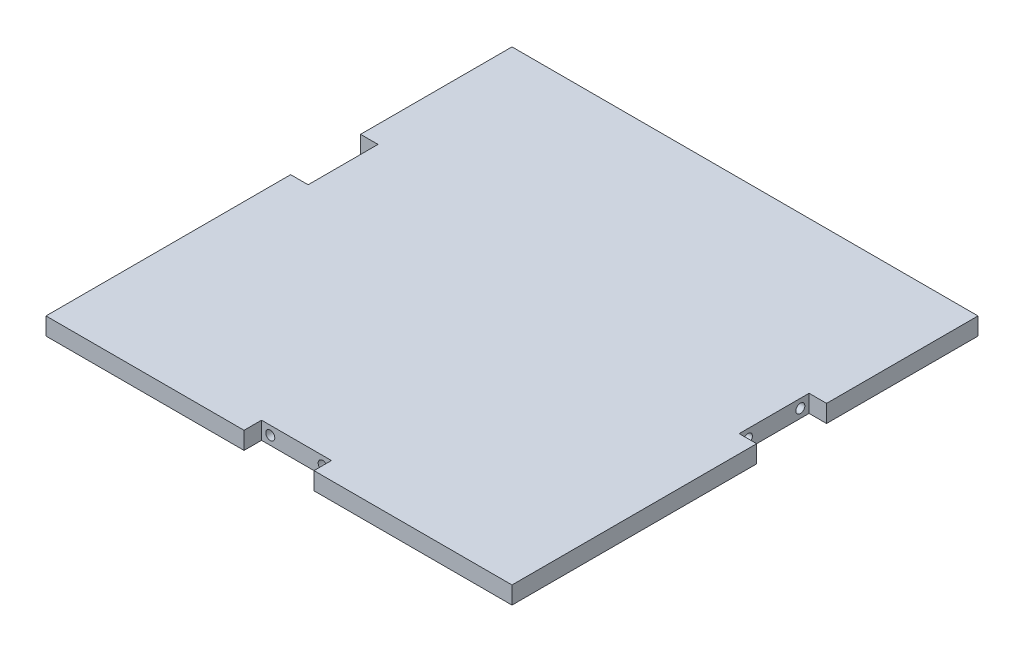
SolidWorks part; units mm, degrees
material "PE High Density"
ref_plane "Front Plane" through (0, 0, 0) normal (0, 0, 1) x (1, 0, 0)
ref_plane "Top Plane" through (0, 0, 0) normal (0, 1, 0) x (1, 0, 0)
ref_plane "Right Plane" through (0, 0, 0) normal (1, 0, 0) x (0, 0, -1)
sketch "Sketch1" plane through (0, 0, 0) normal (0, 1, 0) x (1, 0, 0)
  line L1 (-127, 127) -> (127, 127)
  line L2 (-127, 127) -> (-127, -127)
  line L3 (-127, -127) -> (127, -127)
  line L4 (127, 127) -> (127, -127)
  line L5 (-127, 127) -> (127, -127) construction
  line L6 (-127, -127) -> (127, 127) construction
  point P0 (0, 0)
  dimension "D1" = 254
  dimension "D2" = 254
extrude "Boss-Extrude1" add sketch "Sketch1" along normal blind 9.525
sketch "Sketch7" plane through (0, 9.525, 0) normal (0, 1, 0) x (1, 0, 0)
  line L0 (127, 127) -> (-127, 127) construction
  line L1 (-127, 25.4) -> (-41.0029, 25.4) construction
  line L2 (0, 0) -> (0, -32.6591) construction
  line L3 (-127, 44.45) -> (-117.475, 44.45)
  line L4 (-127, 44.45) -> (-127, 6.35)
  line L5 (-127, 6.35) -> (-117.475, 6.35)
  line L6 (-117.475, 44.45) -> (-117.475, 6.35)
  line L7 (117.475, 44.45) -> (117.475, 6.35)
  line L8 (127, 6.35) -> (117.475, 6.35)
  line L9 (127, 44.45) -> (127, 6.35)
  line L10 (127, 44.45) -> (117.475, 44.45)
  line L11 (0, -127) -> (0, -107.95) construction
  line L13 (-19.05, -127) -> (19.05, -127)
  line L14 (-19.05, -127) -> (-19.05, -117.475)
  line L15 (-127, -127) -> (127, -127) construction
  line L16 (-19.05, -117.475) -> (19.05, -117.475)
  line L17 (19.05, -127) -> (19.05, -117.475)
  point P10 (-117.475, 25.4)
  point P27 (0, -117.475)
  dimension "D1" = 38.1
  dimension "D2" = 9.525
  dimension "D3" = 38.1
  dimension "D4" = 9.525
  dimension "D5" = 82.55
extrude "Cut-Extrude4" cut sketch "Sketch7" against normal through all
sketch3d "3DSketch1"
  line L0 (-117.475, 4.7625, -44.45) -> (-117.475, 4.7625, -6.35) construction
  line L1 (-117.475, 0, -44.45) -> (-117.475, 9.525, -44.45) construction
  line L2 (-117.475, 0, -6.35) -> (-117.475, 9.525, -6.35) construction
  line L3 (-19.05, 4.7625, 117.475) -> (19.05, 4.7625, 117.475) construction
  line L4 (-19.05, 0, 117.475) -> (-19.05, 9.525, 117.475) construction
  line L5 (19.05, 0, 117.475) -> (19.05, 9.525, 117.475) construction
  line L6 (117.475, 4.7625, -6.35) -> (117.475, 4.7625, -44.45) construction
  line L7 (117.475, 0, -6.35) -> (117.475, 9.525, -6.35) construction
  line L8 (117.475, 0, -44.45) -> (117.475, 9.525, -44.45) construction
  point P6 (-117.475, 4.7625, -39.6875)
  point P7 (-117.475, 4.7625, -11.1125)
  point P14 (-14.2875, 4.7625, 117.475)
  point P15 (14.2875, 4.7625, 117.475)
  point P22 (117.475, 4.7625, -11.1125)
  point P23 (117.475, 4.7625, -39.6875)
  dimension "D1" = 4.7625
  dimension "D2" = 4.7625
  dimension "D3" = 4.7625
  dimension "D4" = 4.7625
  dimension "D5" = 4.7625
  dimension "D6" = 4.7625
hole_wizard "#10 (0.1935) Diameter Hole1" positions "Sketch11" profile "Sketch10" hole size "#10" standard "ANSI Inch"
sketch "Sketch11" plane through (117.475, 0, 0) normal (1, 0, 0) x (0, 0, -1)
  point P0 (11.1125, 4.7625)
  point P3 (39.6875, 4.7625)
sketch "Sketch10" plane through (117.475, 4.7625, -11.1125) normal (0, 1, 0) x (0, 0, -1)
  line L0 (0, 0) -> (0, 14.1766)
  line L1 (0, 14.1766) -> (2.4574, 12.7)
  line L2 (2.4574, 12.7) -> (2.4574, 0)
  line L5 (2.4574, 0) -> (0, 0)
  line L10 (0, 14.1766) -> (-2.4575, 12.7) construction
  line L11 (0, -6.35) -> (0, 107.95) construction
  dimension "Hole Dia." = 4.9149
  dimension "Hole Depth" = 12.7
  dimension "Drill Angle" = 118
hole_wizard "#10 (0.1935) Diameter Hole2" positions "Sketch13" profile "Sketch12" hole size "#10" standard "ANSI Inch"
sketch "Sketch13" plane through (0, 0, 117.475) normal (0, 0, 1) x (1, 0, 0)
  point P0 (-14.2875, 4.7625)
  point P3 (14.2875, 4.7625)
sketch "Sketch12" plane through (-14.2875, 4.7625, 117.475) normal (1, 0, 0) x (0, -1, 0)
  line L0 (0, 0) -> (0, 14.1766)
  line L1 (0, 14.1766) -> (2.4574, 12.7)
  line L2 (2.4574, 12.7) -> (2.4574, 0)
  line L5 (2.4574, 0) -> (0, 0)
  line L10 (0, 14.1766) -> (-2.4575, 12.7) construction
  line L11 (0, -6.35) -> (0, 107.95) construction
  dimension "Hole Dia." = 4.9149
  dimension "Hole Depth" = 12.7
  dimension "Drill Angle" = 118
hole_wizard "#10 (0.1935) Diameter Hole3" positions "Sketch15" profile "Sketch14" hole size "#10" standard "ANSI Inch"
sketch "Sketch15" plane through (-117.475, 0, 0) normal (-1, 0, 0) x (0, 0, 1)
  point P0 (-39.6875, 4.7625)
  point P3 (-11.1125, 4.7625)
sketch "Sketch14" plane through (-117.475, 4.7625, -39.6875) normal (0, 1, 0) x (0, 0, 1)
  line L0 (0, 0) -> (0, 14.1766)
  line L1 (0, 14.1766) -> (2.4574, 12.7)
  line L2 (2.4574, 12.7) -> (2.4574, 0)
  line L5 (2.4574, 0) -> (0, 0)
  line L10 (0, 14.1766) -> (-2.4574, 12.7) construction
  line L11 (0, -6.35) -> (0, 107.95) construction
  dimension "Hole Dia." = 4.9149
  dimension "Hole Depth" = 12.7
  dimension "Drill Angle" = 118
